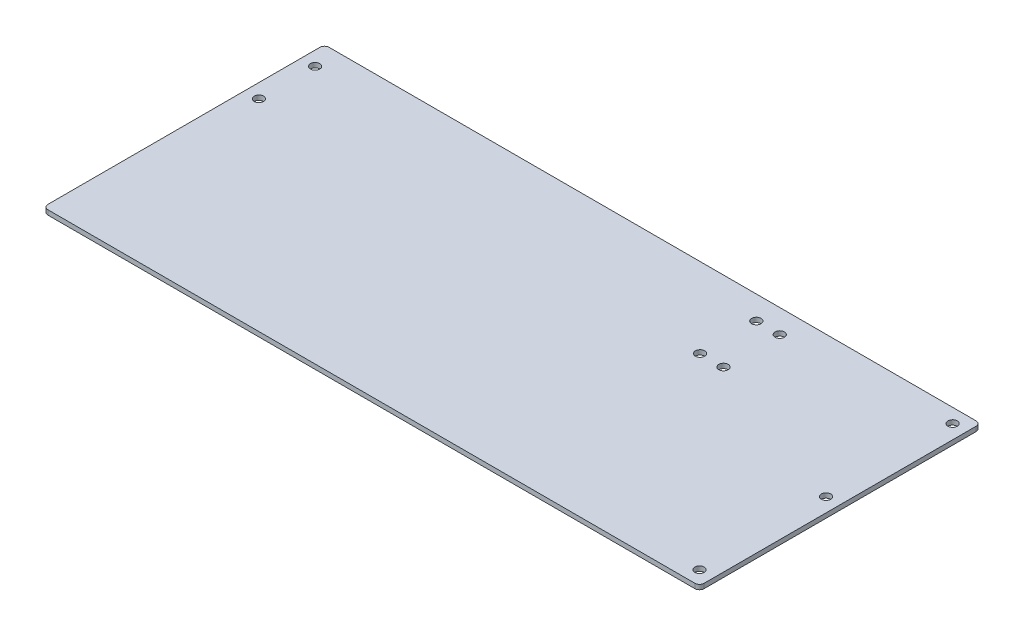
SolidWorks part; units mm, degrees
material "PC High Viscosity"
ref_plane "Front Plane" through (0, 0, 0) normal (0, 0, 1) x (1, 0, 0)
ref_plane "Top Plane" through (0, 0, 0) normal (0, 1, 0) x (1, 0, 0)
ref_plane "Right Plane" through (0, 0, 0) normal (1, 0, 0) x (0, 0, -1)
sketch "Sketch1" plane through (0, 0, 0) normal (0, 1, 0) x (1, 0, 0)
  line L1 (-222.25, 95.25) -> (222.25, 95.25)
  line L2 (-222.25, 95.25) -> (-222.25, -95.25)
  line L3 (-222.25, -95.25) -> (222.25, -95.25)
  line L4 (222.25, 95.25) -> (222.25, -95.25)
  line L5 (-222.25, 95.25) -> (222.25, -95.25) construction
  line L6 (-222.25, -95.25) -> (222.25, 95.25) construction
  point P0 (0, 0)
  dimension "D1" = 190.5
  dimension "D2" = 444.5
extrude "Boss-Extrude1" add sketch "Sketch1" along normal blind 3.175
hole_wizard "1/4 (0.25) Diameter Hole1" positions "Sketch2" profile "Sketch3" hole size "1/4" standard "ANSI Inch" end condition through all
sketch "Sketch2" plane through (0, 3.175, 0) normal (0, 1, 0) x (1, 0, 0)
  line L2 (222.25, 95.25) -> (-222.25, 95.25) construction
  line L3 (-222.25, 95.25) -> (-222.25, -95.25) construction
  point P0 (-212.725, 79.375)
  point P2 (-212.725, 41.275)
  point P4 (101.981, 79.375)
  point P6 (101.981, 41.275)
  point P20 (86.106, 79.375)
  point P22 (86.106, 41.275)
  dimension "D1" = 15.875
  dimension "D2" = 38.1
  dimension "D3" = 314.706
  dimension "D4" = 9.525
  dimension "D5" = 15.875
sketch "Sketch3" plane through (-212.725, 3.175, -79.375) normal (1, 0, 0) x (0, 0, 1)
  line L0 (0, 0) -> (0, 3.175)
  line L1 (0, 3.175) -> (3.175, 3.175)
  line L2 (3.175, 3.175) -> (3.175, 0)
  line L5 (3.175, 0) -> (0, 0)
  line L11 (0, -6.35) -> (0, 107.95) construction
  dimension "Thru Hole Dia." = 6.35
  dimension "Thru Hole Depth" = 3.175
fillet "Fillet1" radius 3.175 4 edges at (222.25, 1.5875, -95.25) (222.25, 1.5875, 95.25) (-222.25, 1.5875, 95.25) (-222.25, 1.5875, -95.25)
hole_wizard "1/4 (0.25) Diameter Hole2" positions "Sketch4" profile "Sketch5" hole size "1/4" standard "ANSI Inch" end condition through all
sketch "Sketch4" plane through (0, 0, 0) normal (0, -1, 0) x (-1, 0, 0)
  line L0 (-222.25, -92.075) -> (-222.25, 92.075) construction
  point P0 (-212.725, 85.725)
  point P2 (-212.725, 0)
  point P4 (-212.725, -85.725)
  dimension "D2" = 85.725
  dimension "D1" = 85.725
  dimension "D3" = 9.525
sketch "Sketch5" plane through (212.725, 0, -85.725) normal (1, 0, 0) x (0, 0, -1)
  line L0 (0, 0) -> (0, 3.175)
  line L1 (0, 3.175) -> (3.175, 3.175)
  line L2 (3.175, 3.175) -> (3.175, 0)
  line L5 (3.175, 0) -> (0, 0)
  line L11 (0, -6.35) -> (0, 107.95) construction
  dimension "Thru Hole Dia." = 6.35
  dimension "Thru Hole Depth" = 3.175
equation "\"D2@Sketch4\"=\"D1@Sketch4\""
